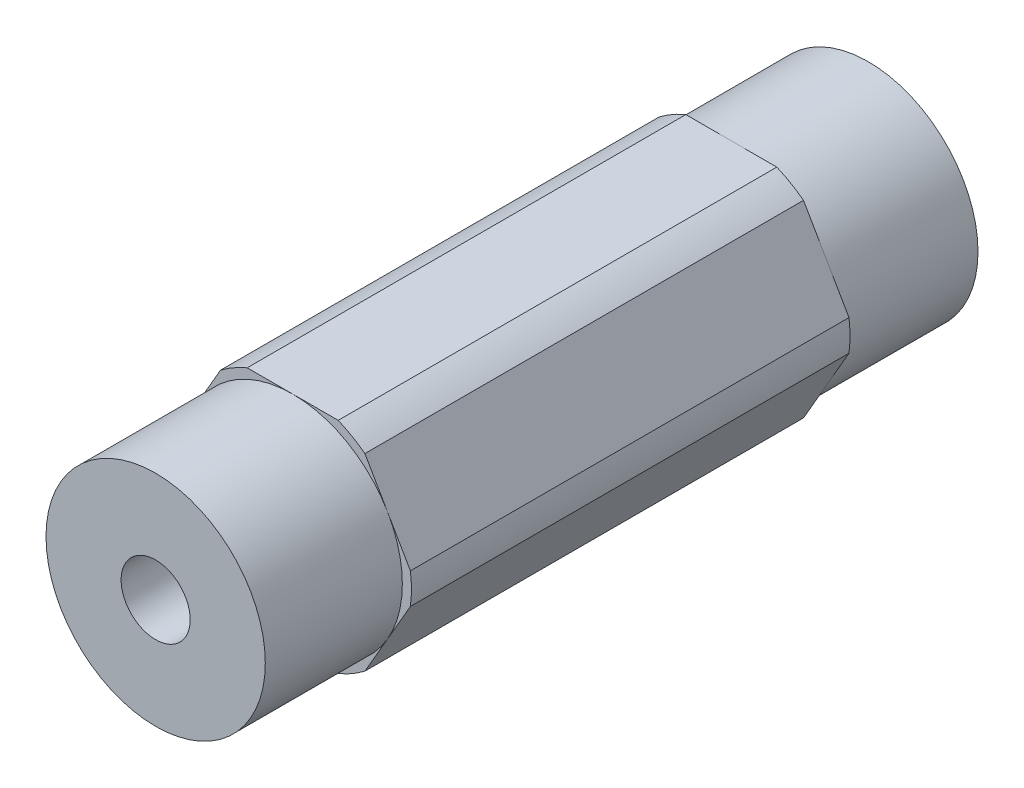
SolidWorks part; units mm, degrees
material "6061-T6 (SS)"
ref_plane "Front Plane" through (0, 0, 0) normal (0, 0, 1) x (1, 0, 0)
ref_plane "Top Plane" through (0, 0, 0) normal (0, 1, 0) x (1, 0, 0)
ref_plane "Right Plane" through (0, 0, 0) normal (1, 0, 0) x (0, 0, -1)
sketch "Sketch1" plane through (0, 0, 0) normal (0, 0, 1) x (1, 0, 0)
  line L1 (3.6662, 6.35) -> (-3.6662, 6.35)
  line L2 (-3.6662, 6.35) -> (-7.3323, 0)
  line L3 (-7.3323, 0) -> (-3.6662, -6.35)
  line L4 (-3.6662, -6.35) -> (3.6662, -6.35)
  line L5 (3.6662, -6.35) -> (7.3323, 0)
  line L6 (7.3323, 0) -> (3.6662, 6.35)
  circle A0 centre (0, 0) radius 6.35 construction
  circle A1 centre (0, 0) radius 2
  circle A2 centre (0, 0) radius 6.875
  point P1 (0, 6.35)
  dimension "D2" = 13.75
  dimension "D3" = 4
  dimension "D1" = 12.7
extrude "Boss-Extrude1" add sketch "Sketch1" along normal mid plane 25.4 contours L6 A2 L1 L2 L3 L4 L5 A1 region at (3.3439, 5.7918, 0)
sketch "Sketch4" plane through (0, 0, 12.7) normal (0, 0, 1) x (1, 0, 0)
  circle A0 centre (0, 0) radius 6.35
  circle A1 centre (0, 0) radius 2 construction
  circle A2 centre (0, 0) radius 2
  dimension "D1" = 12.7
extrude "Boss-Extrude2" add sketch "Sketch4" along normal blind 7.9375
mirror "Mirror1" about plane through (0, 0, 0) normal (0, 0, 1) of "Boss-Extrude2"
equation "\"D2@Sketch1\"=13.75mm"
equation "\"D3@Sketch1\"=4mm"
